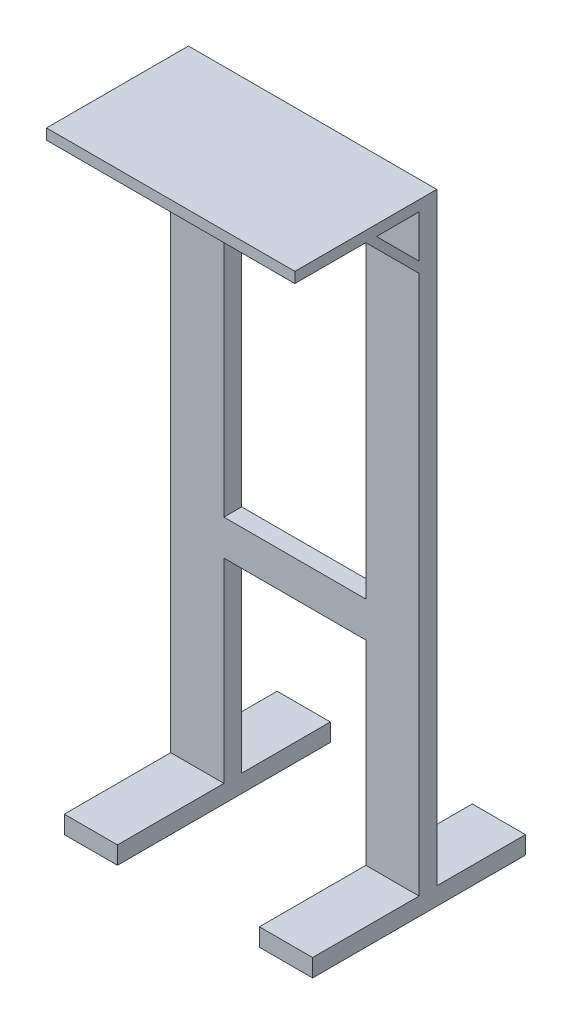
SolidWorks part; units mm, degrees
ref_plane "Alzado" through (0, 0, 0) normal (0, 0, 1) x (1, 0, 0)
ref_plane "Planta" through (0, 0, 0) normal (0, 1, 0) x (1, 0, 0)
ref_plane "Vista lateral" through (0, 0, 0) normal (1, 0, 0) x (0, 0, -1)
sketch "Croquis1" plane through (0, 0, 0) normal (0, 0, 1) x (1, 0, 0)
  line L0 (550, 50) -> (700, 50)
  line L1 (0, 0) -> (150, 0)
  line L2 (0, 0) -> (0, 50)
  line L3 (0, 50) -> (150, 50)
  line L4 (700, 0) -> (700, 50)
  line L5 (0, 50) -> (150, 50)
  line L6 (0, 50) -> (0, 0)
  line L7 (0, 0) -> (150, 0)
  line L8 (150, 50) -> (150, 0)
  line L9 (700, 50) -> (550, 50)
  line L10 (700, 50) -> (700, 0)
  line L11 (700, 0) -> (550, 0)
  line L12 (550, 50) -> (550, 0)
  line L13 (550, 0) -> (700, 0)
  point P7 (550.0894, 52.3384)
  point P10 (574.6113, 0)
  point P11 (639.0155, 0)
  dimension "D1" = 700
  dimension "D2" = 50
extrude "Saliente-Extruir1" add sketch "Croquis1" along normal blind 300 and the other way blind 300 contours L6 L5 L8 L7 | L10 L9 L12 L11
sketch "Croquis2" plane through (0, 50, 0) normal (0, 1, 0) x (1, 0, 0)
  line L0 (700, 300) -> (700, -300) construction
  line L1 (0, 0) -> (150, 0)
  line L2 (0, 0) -> (0, 50)
  line L3 (0, 50) -> (150, 50)
  line L4 (700, 0) -> (700, 50)
  line L5 (150, 300) -> (150, -300) construction
  line L6 (0, 50) -> (150, 50)
  line L7 (0, 50) -> (0, 0)
  line L8 (0, 0) -> (150, 0)
  line L9 (150, 50) -> (150, 0)
  line L10 (550, 300) -> (550, -300) construction
  line L11 (700, 50) -> (550, 50)
  line L12 (700, 50) -> (700, 0)
  line L13 (700, 0) -> (550, 0)
  line L14 (550, 50) -> (550, 0)
  line L15 (550, 50) -> (700, 50)
  line L16 (550, 0) -> (700, 0)
  dimension "D1" = 50
extrude "Saliente-Extruir2" add sketch "Croquis2" along normal blind 1700 contours L7 L6 L9 L8 | L12 L11 L14 L13
sketch "Croquis3" plane through (0, 0, 0) normal (0, 0, 1) x (1, 0, 0)
  line L0 (625, 50) -> (625, 600) construction
  line L1 (700, 50) -> (550, 50) construction
  line L2 (700, 1750) -> (700, 50) construction
  line L3 (700, 600) -> (0, 600)
  line L4 (700, 600) -> (700, 700)
  line L5 (700, 700) -> (0, 700)
  line L6 (0, 600) -> (0, 700)
  line L7 (0, 1750) -> (0, 50) construction
  line L9 (0, 1750) -> (700, 1750)
  line L10 (0, 1750) -> (0, 1650)
  line L11 (0, 1650) -> (700, 1650)
  line L12 (700, 1750) -> (700, 1650)
  point P17 (700, 1750)
extrude "Saliente-Extruir3" add sketch "Croquis3" against normal blind 50
sketch "Croquis4" plane through (0, 0, 0) normal (0, 0, 1) x (1, 0, 0)
  line L0 (700, 50) -> (700, 1750) construction
  line L1 (0, 1750) -> (700, 1750)
  line L2 (0, 1750) -> (0, 1720)
  line L3 (0, 1720) -> (700, 1720)
  line L4 (700, 1750) -> (700, 1720)
extrude "Saliente-Extruir4" add sketch "Croquis4" along normal blind 350
sketch "Croquis5" plane through (0, 0, 0) normal (-1, 0, 0) x (0, 0, 1)
  line L1 (0, 1720) -> (0, 50) construction
  line L3 (350, 1720) -> (0, 1720) construction
  line L4 (0, 1570) -> (150, 1720)
  line L5 (150, 1720) -> (120, 1720)
  line L6 (0, 1570) -> (0, 1600)
  line L7 (0, 1600) -> (120, 1720)
extrude "Saliente-Extruir5" add sketch "Croquis5" against normal blind 15
sketch "Croquis6" plane through (700, 0, 0) normal (1, 0, 0) x (0, 0, -1)
  line L0 (0, 1570) -> (0, 1600)
  line L1 (0, 1600) -> (-120, 1720)
  line L2 (-120, 1720) -> (-150, 1720)
  line L3 (-150, 1720) -> (0, 1570)
extrude "Saliente-Extruir6" add sketch "Croquis6" against normal blind 15
